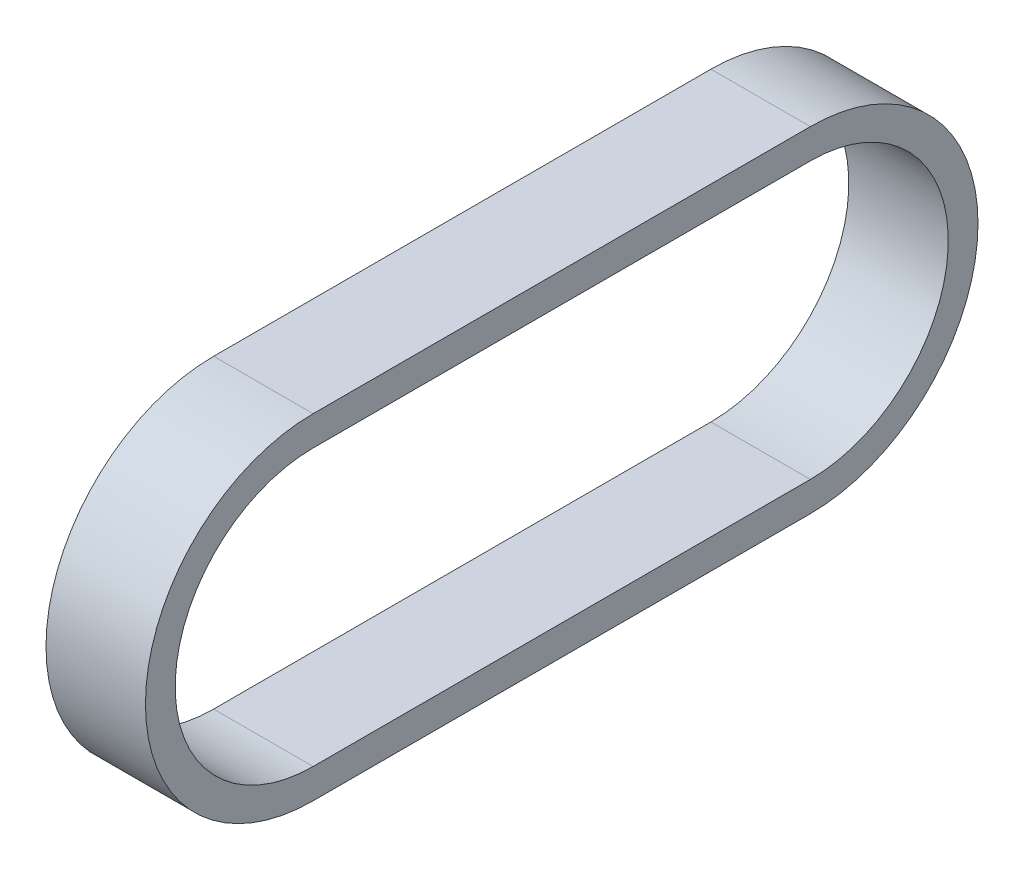
SolidWorks part; units mm, degrees
ref_plane "Front" through (0, 0, 0) normal (0, 0, 1) x (1, 0, 0)
ref_plane "Top" through (0, 0, 0) normal (0, 1, 0) x (1, 0, 0)
ref_plane "Right" through (0, 0, 0) normal (1, 0, 0) x (0, 0, -1)
sketch "Sketch1" plane through (0, 0, 0) normal (1, 0, 0) x (0, 0, -1)
  line L0 (-21.2471, 0) -> (21.2471, 0) construction
  line L1 (-21.2471, 14.3256) -> (21.2471, 14.3256)
  line L2 (-21.2471, -14.3256) -> (21.2471, -14.3256)
  arc A0 (-21.2471, 14.3256) -> (-21.2471, -14.3256) centre (-21.2471, 0) ccw
  arc A1 (21.2471, -14.3256) -> (21.2471, 14.3256) centre (21.2471, 0) ccw
  point P2 (0, 0)
  dimension "D2" = 28.6512
  dimension "D1" = 42.4942
extrude "Extrude-Thin1" add sketch "Sketch1" along normal blind 8.5 thin thin type one direction reverse wall 2.54
